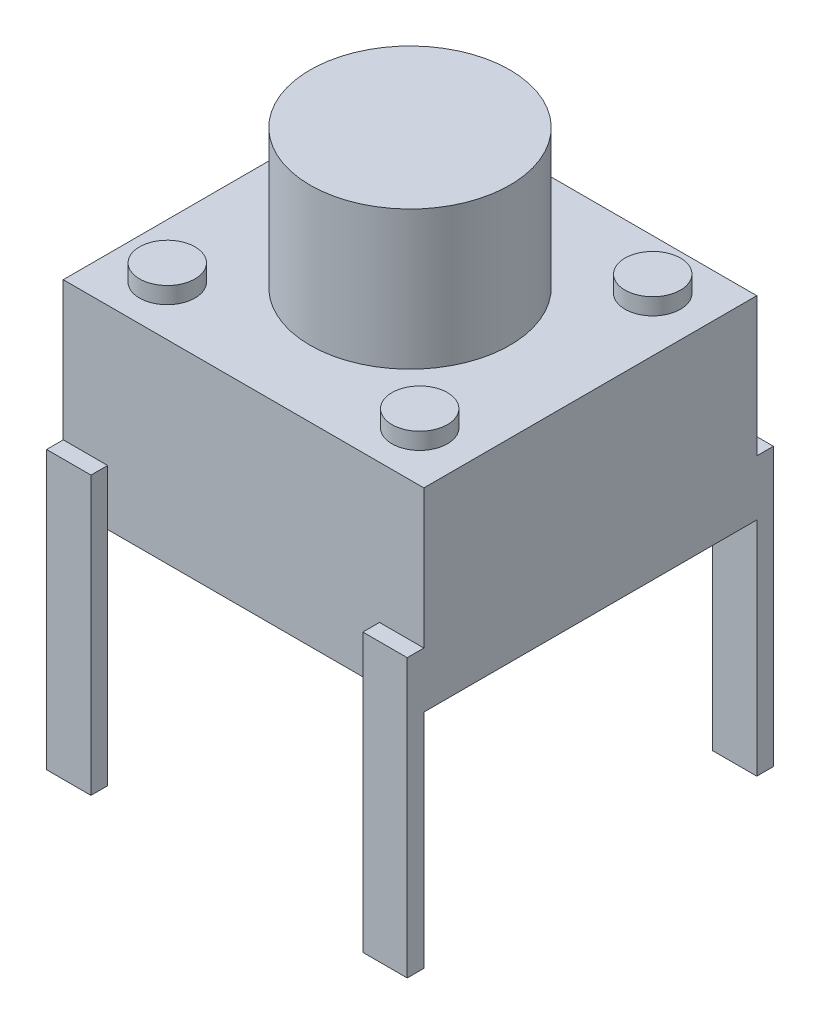
SolidWorks part; units mm, degrees
ref_plane "前视基准面" through (0, 0, 0) normal (0, 0, 1) x (1, 0, 0)
ref_plane "上视基准面" through (0, 0, 0) normal (0, 1, 0) x (1, 0, 0)
ref_plane "右视基准面" through (0, 0, 0) normal (1, 0, 0) x (0, 0, -1)
other "Configuration Table"
sketch "草图1" plane through (0, 0, 0) normal (0, 1, 0) x (1, 0, 0)
  line L1 (-3.25, -3) -> (3.25, -3)
  line L2 (-3.25, -3) -> (-3.25, 3)
  line L3 (-3.25, 3) -> (3.25, 3)
  line L4 (3.25, -3) -> (3.25, 3)
  line L5 (-3.25, -3) -> (3.25, 3) construction
  line L6 (-3.25, 3) -> (3.25, -3) construction
  circle A0 centre (0, 0) radius 1.8
  circle A1 centre (-2.275, 2.1) radius 0.5
  circle A2 centre (-2.275, -2.1) radius 0.5
  circle A3 centre (2.275, -2.1) radius 0.5
  circle A4 centre (2.275, 2.1) radius 0.5
  point P0 (0, 0)
  dimension "D3" = 3.6
  dimension "D5" = 1
  dimension "D1" = 6
  dimension "D2" = 6.5
  dimension "D4" = 4.2
extrude "凸台-拉伸1" add sketch "草图1" along normal blind 3.5 contours L3 L4 L1 L2
extrude "凸台-拉伸2" add sketch "草图1<3>" along normal blind 6 contours A0
sketch "草图1<3>" plane through (0, 0, 0) normal (0, 1, 0) x (1, 0, 0) same geometry as "草图1"
extrude "凸台-拉伸3" add sketch "草图1<4>" along normal blind 0.3 from surface contours A1 | A2 | A4 | A3 starting at face at (0, 3.5, -1.8)
sketch "草图1<4>" plane through (0, 0, 0) normal (0, 1, 0) x (1, 0, 0) same geometry as "草图1"
sketch "草图2" plane through (0, 0, 0) normal (0, -1, 0) x (1, 0, 0)
  line L1 (-3.25, 3) -> (-2.45, 3)
  line L2 (-3.25, 3) -> (-3.25, 3.3)
  line L3 (-3.25, 3.3) -> (-2.45, 3.3)
  line L4 (-2.45, 3) -> (-2.45, 3.3)
  line L5 (-3.25, -3) -> (3.25, -3) construction
  line L6 (3.25, 3) -> (2.45, 3)
  line L7 (3.25, 3) -> (3.25, 3.3)
  line L8 (3.25, 3.3) -> (2.45, 3.3)
  line L9 (2.45, 3) -> (2.45, 3.3)
  line L10 (-3.25, -3) -> (-2.45, -3)
  line L11 (-3.25, -3) -> (-3.25, -3.3)
  line L12 (-3.25, -3.3) -> (-2.45, -3.3)
  line L13 (-2.45, -3) -> (-2.45, -3.3)
  line L15 (2.45, -3) -> (3.25, -3)
  line L16 (2.45, -3) -> (2.45, -3.3)
  line L17 (2.45, -3.3) -> (3.25, -3.3)
  line L18 (3.25, -3) -> (3.25, -3.3)
  point P4 (0, 0)
  point P20 (0, 0)
  dimension "D1" = 0.3
  dimension "D2" = 0.8
extrude "凸台-拉伸4" add sketch "草图2" along normal blind 5 from offset 1 offset against normal yes
